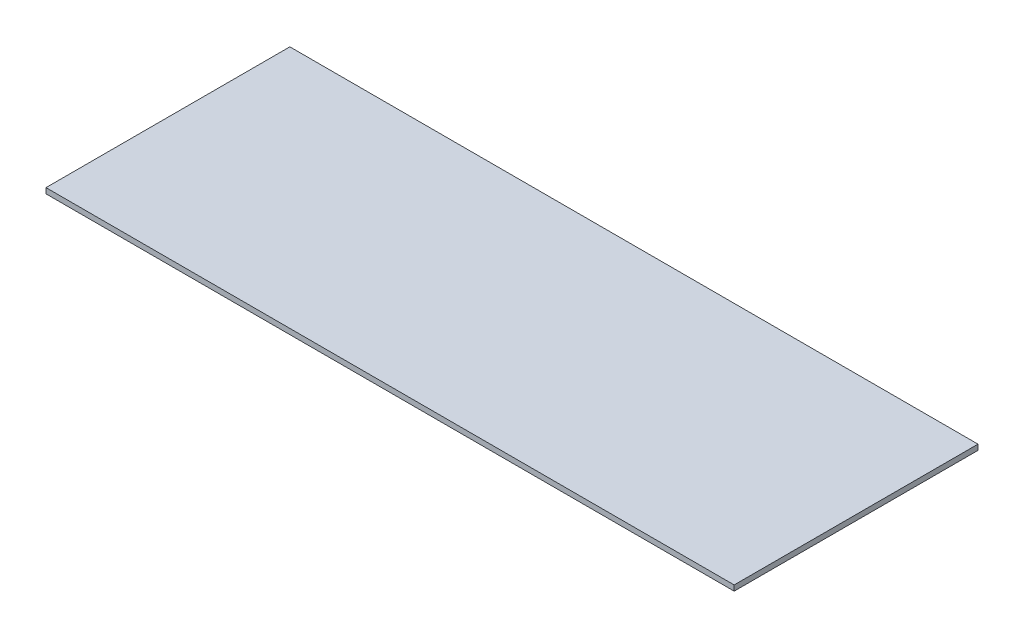
SolidWorks part; units mm, degrees
ref_plane "Front Plane" through (0, 0, 0) normal (0, 0, 1) x (1, 0, 0)
ref_plane "Top Plane" through (0, 0, 0) normal (0, 1, 0) x (1, 0, 0)
ref_plane "Right Plane" through (0, 0, 0) normal (1, 0, 0) x (0, 0, -1)
sketch "Sketch1" plane through (0, 0, 0) normal (0, 1, 0) x (1, 0, 0)
  line L1 (0, 0) -> (508, 0)
  line L2 (0, 0) -> (0, 180)
  line L3 (0, 180) -> (508, 180)
  line L4 (508, 0) -> (508, 180)
  dimension "D1" = 180
  dimension "D2" = 508
extrude "Boss-Extrude1" add sketch "Sketch1" along normal blind 4
equation "\"cf_tube_outer_diameter\" = 25mm"
equation "\"cf_tube_inner_diameter\" = 21mm"
equation "\"mid_plate_mid_to_top\" = 100mm"
equation "\"mid_plate_mid_to_bottom\" = 30mm"
equation "\"mid_plate_horizontal_spacing\" = 250mm"
equation "\"cf_plate_thickness\" = 4mm"
equation "\"mid_tube_length\" = 500mm"
equation "\"mid_plate_bottom_width\"= 180mm"
equation "\"D1@Sketch1\"=\"mid_plate_bottom_width\""
equation "\"D2@Sketch1\"=\"mid_tube_length\"+\"cf_plate_thickness\"*2"
equation "\"D1@Boss-Extrude1\"=\"cf_plate_thickness\""
